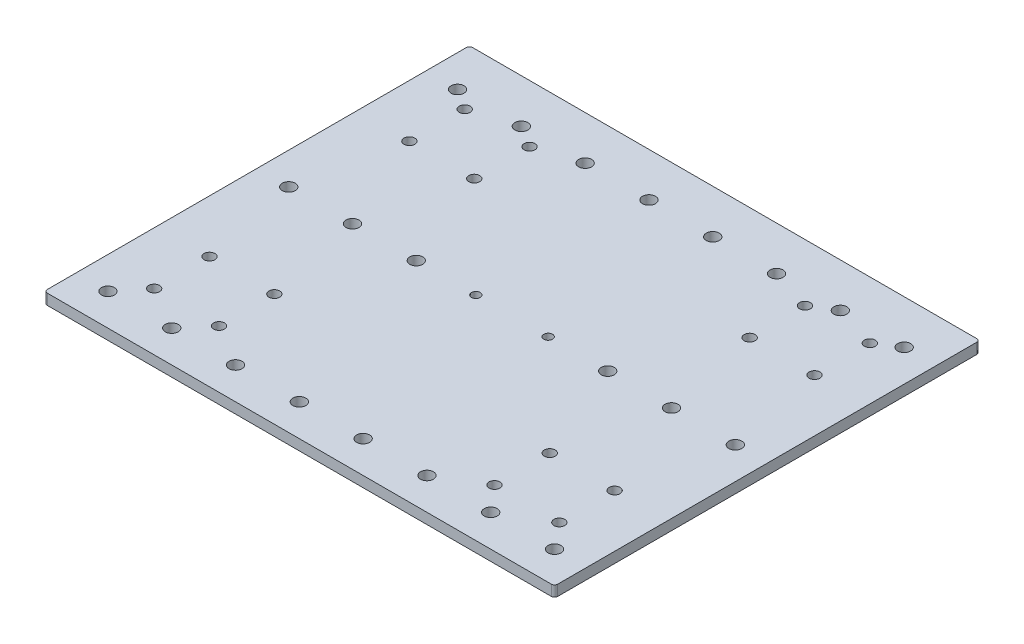
SolidWorks part; units mm, degrees
ref_plane "Front Plane" through (0, 0, 0) normal (0, 0, 1) x (1, 0, 0)
ref_plane "Top Plane" through (0, 0, 0) normal (0, 1, 0) x (1, 0, 0)
ref_plane "Right Plane" through (0, 0, 0) normal (1, 0, 0) x (0, 0, -1)
sketch "Sketch1" plane through (0, 0, 0) normal (0, 1, 0) x (1, 0, 0)
  line L1 (-120, -100) -> (120, -100)
  line L2 (-120, -100) -> (-120, 100)
  line L3 (-120, 100) -> (120, 100)
  line L4 (120, -100) -> (120, 100)
  line L5 (-120, -100) -> (120, 100) construction
  line L6 (-120, 100) -> (120, -100) construction
  point P0 (0, 0)
  dimension "D1" = 240
  dimension "D2" = 200
extrude "Boss-Extrude1" add sketch "Sketch1" along normal mid plane 5
sketch "Sketch2" plane through (0, 2.5, 0) normal (0, 1, 0) x (1, 0, 0)
  line L5 (-80, 100) -> (-80, -100)
  line L6 (-80, 100) -> (-80, -100) construction
  line L8 (80, -100) -> (80, 100)
  line L9 (80, -100) -> (80, 100) construction
  line L11 (120, 60) -> (-120, 60)
  line L12 (120, 60) -> (-120, 60) construction
  line L14 (-120, -60) -> (120, -60)
  line L15 (-120, -60) -> (120, -60) construction
  line L16 (-95.25, 73) -> (-64.75, 73) construction
  line L17 (-95.25, 73) -> (-95.25, 47) construction
  line L18 (-95.25, 47) -> (-64.75, 47) construction
  line L19 (-64.75, 73) -> (-64.75, 47) construction
  line L20 (-95.25, 73) -> (-64.75, 47) construction
  line L21 (-95.25, 47) -> (-64.75, 73) construction
  line L22 (64.75, 47) -> (95.25, 47) construction
  line L23 (64.75, 47) -> (64.75, 73) construction
  line L24 (64.75, 73) -> (95.25, 73) construction
  line L25 (95.25, 47) -> (95.25, 73) construction
  line L26 (64.75, 47) -> (95.25, 73) construction
  line L27 (64.75, 73) -> (95.25, 47) construction
  line L28 (64.75, -47) -> (95.25, -47) construction
  line L29 (64.75, -47) -> (64.75, -73) construction
  line L30 (64.75, -73) -> (95.25, -73) construction
  line L31 (95.25, -47) -> (95.25, -73) construction
  line L32 (64.75, -47) -> (95.25, -73) construction
  line L33 (64.75, -73) -> (95.25, -47) construction
  line L34 (-95.25, -73) -> (-64.75, -73) construction
  line L35 (-95.25, -73) -> (-95.25, -47) construction
  line L36 (-95.25, -47) -> (-64.75, -47) construction
  line L37 (-64.75, -73) -> (-64.75, -47) construction
  line L38 (-95.25, -73) -> (-64.75, -47) construction
  line L39 (-95.25, -47) -> (-64.75, -73) construction
  circle A0 centre (-95.25, 73) radius 2.55
  circle A1 centre (-95.25, 47) radius 2.55
  circle A2 centre (-64.75, 73) radius 2.55
  circle A3 centre (-64.75, 47) radius 2.55
  circle A4 centre (-95.25, -47) radius 2.55
  circle A5 centre (-95.25, -73) radius 2.55
  circle A6 centre (-64.75, -73) radius 2.55
  circle A7 centre (-64.75, -47) radius 2.55
  circle A8 centre (95.25, -47) radius 2.55
  circle A9 centre (64.75, -47) radius 2.55
  circle A10 centre (64.75, -73) radius 2.55
  circle A11 centre (95.25, -73) radius 2.55
  circle A12 centre (64.75, 73) radius 2.55
  circle A13 centre (64.75, 47) radius 2.55
  circle A14 centre (95.25, 73) radius 2.55
  circle A15 centre (95.25, 47) radius 2.55
  point P0 (-80, 60)
  point P13 (80, 60)
  point P18 (80, -60)
  point P23 (-80, -60)
  dimension "D13" = 5.1
  dimension "D14" = 5.1
  dimension "D15" = 5.1
  dimension "D16" = 5.1
  dimension "D17" = 5.1
  dimension "D18" = 5.1
  dimension "D19" = 5.1
  dimension "D20" = 5.1
  dimension "D21" = 5.1
  dimension "D22" = 5.1
  dimension "D23" = 5.1
  dimension "D24" = 5.1
  dimension "D25" = 5.1
  dimension "D26" = 5.1
  dimension "D27" = 5.1
  dimension "D28" = 5.1
  dimension "D1" = 40
  dimension "D5" = 30.5
  dimension "D6" = 26
  dimension "D7" = 30.5
  dimension "D8" = 26
  dimension "D9" = 26
  dimension "D10" = 30.5
  dimension "D11" = 26
  dimension "D12" = 30.5
  dimension "D2" = 40
  dimension "D3" = 40
  dimension "D4" = 40
extrude "Cut-Extrude1" cut sketch "Sketch2" against normal through all
sketch "Sketch3" plane through (0, 2.5, 0) normal (0, 1, 0) x (1, 0, 0)
  line L3 (-17, 0) -> (17, 0) construction
  circle A0 centre (-17, 0) radius 2.05
  circle A1 centre (17, 0) radius 2.05
  point P0 (0, 0)
  dimension "D3" = 4.1
  dimension "D4" = 4.1
  dimension "D1" = 34
extrude "Cut-Extrude2" cut sketch "Sketch3" against normal through all
sketch "Sketch4" plane through (0, 2.5, 0) normal (0, 1, 0) x (1, 0, 0)
  line L0 (-105, 100) -> (-105, -100) construction
  line L1 (120, 100) -> (-120, 100) construction
  line L2 (-120, -100) -> (120, -100) construction
  line L3 (-120, 100) -> (-120, -100) construction
  line L4 (-75, 100) -> (-75, -100) construction
  line L5 (-45, 100) -> (-45, -100) construction
  line L6 (-15, 100) -> (-15, -100) construction
  line L7 (15, 100) -> (15, -100) construction
  line L8 (45, 100) -> (45, -100) construction
  line L9 (75, 100) -> (75, -100) construction
  line L10 (105, 100) -> (105, -100) construction
  line L11 (-120, -85) -> (120, -85) construction
  line L12 (-120, 100) -> (-120, -100) construction
  line L13 (120, -100) -> (120, 100) construction
  line L14 (-120, 79.3935) -> (120, 79.3935) construction
  line L15 (-120, 0) -> (120, 0) construction
  circle A0 centre (-105, 79.3935) radius 3.05
  circle A1 centre (-75, 79.3935) radius 3.05
  circle A2 centre (-45, 79.3935) radius 3.05
  circle A3 centre (-15, 79.3935) radius 3.05
  circle A4 centre (15, 79.3935) radius 3.05
  circle A5 centre (45, 79.3935) radius 3.05
  circle A6 centre (75, 79.3935) radius 3.05
  circle A7 centre (105, 79.3935) radius 3.05
  circle A8 centre (-105, 0) radius 3.05
  circle A9 centre (-105, -85) radius 3.05
  circle A10 centre (-75, 0) radius 3.05
  circle A11 centre (-45, 0) radius 3.05
  circle A14 centre (45, 0) radius 3.05
  circle A15 centre (75, 0) radius 3.05
  circle A16 centre (105, 0) radius 3.05
  circle A17 centre (-75, -85) radius 3.05
  circle A18 centre (-45, -85) radius 3.05
  circle A19 centre (-15, -85) radius 3.05
  circle A20 centre (15, -85) radius 3.05
  circle A21 centre (45, -85) radius 3.05
  circle A22 centre (75, -85) radius 3.05
  circle A23 centre (105, -85) radius 3.05
  circle A24 centre (-15, 0) radius 3.05 [skipped]
  circle A25 centre (15, 0) radius 3.05 [skipped]
  point P6 (-120, 0)
  dimension "D3" = 6.1
  dimension "D4" = 6.1
  dimension "D5" = 6.1
  dimension "D1" = 15
  dimension "D2" = 15
  dimension "D6" = 8
extrude "Cut-Extrude3" cut sketch "Sketch4" against normal through all
fillet "Fillet1" radius 1.5 4 edges at (-120, 0, -100) (120, 0, -100) (-120, 0, 100) (120, 0, 100)
equation "\"D4@Sketch4\"=\"D3@Sketch4\""
equation "\"D5@Sketch4\"=\"D3@Sketch4\""
